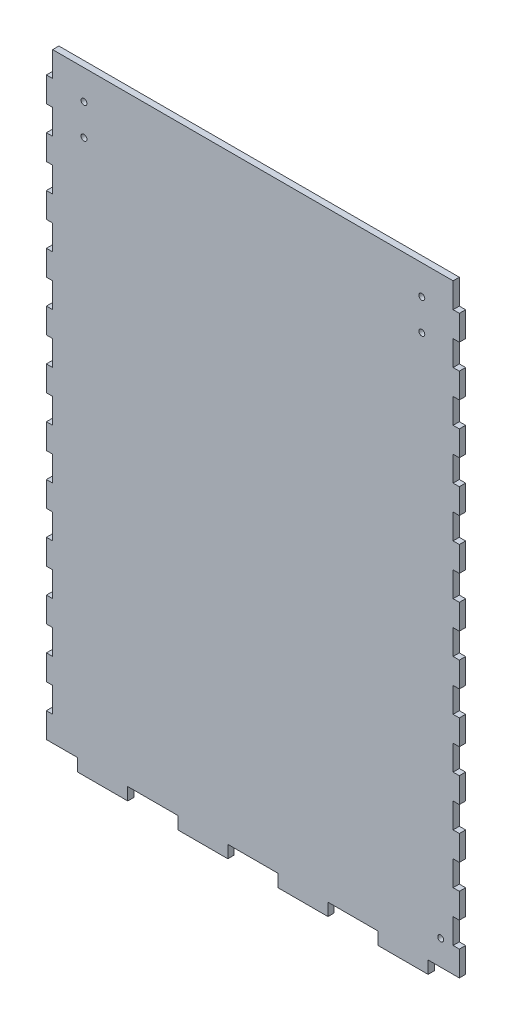
SolidWorks part; units mm, degrees
material "Acrylic (Medium-high impact)"
ref_plane "Front Plane" through (0, 0, 0) normal (0, 0, 1) x (1, 0, 0)
ref_plane "Top Plane" through (0, 0, 0) normal (0, 1, 0) x (1, 0, 0)
ref_plane "Right Plane" through (0, 0, 0) normal (1, 0, 0) x (0, 0, -1)
sketch "Sketch1" plane through (0, 0, 0) normal (0, 0, 1) x (1, 0, 0)
  line L0 (0, 0) -> (203.2, 0)
  line L1 (203.2, 0) -> (203.2, 304.8)
  line L2 (203.2, 304.8) -> (0, 304.8)
  line L3 (0, 304.8) -> (0, 0)
  dimension "D1" = 203.2
  dimension "D2" = 304.8
extrude "Boss-Extrude1" add sketch "Sketch1" along normal blind 3.175
sketch "Sketch2" plane through (0, 0, 3.175) normal (0, 0, 1) x (1, 0, 0)
  line L0 (0, 304.8) -> (-3.175, 304.8)
  line L1 (-3.175, 304.8) -> (-3.175, 292.1)
  line L2 (-3.175, 292.1) -> (0, 292.1)
  line L3 (0, 304.8) -> (0, 0) construction
  line L4 (0, 292.1) -> (0, 304.8)
  line L5 (101.6, 304.8) -> (101.6, 0) construction
  line L6 (203.2, 304.8) -> (0, 304.8) construction
  line L7 (0, 0) -> (203.2, 0) construction
  line L8 (206.375, 292.1) -> (203.2, 292.1)
  line L9 (206.375, 304.8) -> (206.375, 292.1)
  line L10 (203.2, 304.8) -> (206.375, 304.8)
  line L11 (203.2, 292.1) -> (203.2, 304.8)
  line L12 (0, 266.7) -> (0, 279.4)
  line L13 (0, 279.4) -> (-3.175, 279.4)
  line L14 (-3.175, 279.4) -> (-3.175, 266.7)
  line L15 (-3.175, 266.7) -> (0, 266.7)
  line L16 (206.375, 266.7) -> (203.2, 266.7)
  line L17 (203.2, 266.7) -> (203.2, 279.4)
  line L18 (203.2, 279.4) -> (206.375, 279.4)
  line L19 (206.375, 279.4) -> (206.375, 266.7)
  line L20 (0, 241.3) -> (0, 254)
  line L21 (0, 254) -> (-3.175, 254)
  line L22 (-3.175, 254) -> (-3.175, 241.3)
  line L23 (-3.175, 241.3) -> (0, 241.3)
  line L24 (206.375, 241.3) -> (203.2, 241.3)
  line L25 (203.2, 241.3) -> (203.2, 254)
  line L26 (203.2, 254) -> (206.375, 254)
  line L27 (206.375, 254) -> (206.375, 241.3)
  line L28 (0, 215.9) -> (0, 228.6)
  line L29 (0, 228.6) -> (-3.175, 228.6)
  line L30 (-3.175, 228.6) -> (-3.175, 215.9)
  line L31 (-3.175, 215.9) -> (0, 215.9)
  line L32 (206.375, 215.9) -> (203.2, 215.9)
  line L33 (203.2, 215.9) -> (203.2, 228.6)
  line L34 (203.2, 228.6) -> (206.375, 228.6)
  line L35 (206.375, 228.6) -> (206.375, 215.9)
  line L36 (0, 190.5) -> (0, 203.2)
  line L37 (0, 203.2) -> (-3.175, 203.2)
  line L38 (-3.175, 203.2) -> (-3.175, 190.5)
  line L39 (-3.175, 190.5) -> (0, 190.5)
  line L40 (206.375, 190.5) -> (203.2, 190.5)
  line L41 (203.2, 190.5) -> (203.2, 203.2)
  line L42 (203.2, 203.2) -> (206.375, 203.2)
  line L43 (206.375, 203.2) -> (206.375, 190.5)
  line L44 (0, 165.1) -> (0, 177.8)
  line L45 (0, 177.8) -> (-3.175, 177.8)
  line L46 (-3.175, 177.8) -> (-3.175, 165.1)
  line L47 (-3.175, 165.1) -> (0, 165.1)
  line L48 (206.375, 165.1) -> (203.2, 165.1)
  line L49 (203.2, 165.1) -> (203.2, 177.8)
  line L50 (203.2, 177.8) -> (206.375, 177.8)
  line L51 (206.375, 177.8) -> (206.375, 165.1)
  line L52 (0, 139.7) -> (0, 152.4)
  line L53 (0, 152.4) -> (-3.175, 152.4)
  line L54 (-3.175, 152.4) -> (-3.175, 139.7)
  line L55 (-3.175, 139.7) -> (0, 139.7)
  line L56 (206.375, 139.7) -> (203.2, 139.7)
  line L57 (203.2, 139.7) -> (203.2, 152.4)
  line L58 (203.2, 152.4) -> (206.375, 152.4)
  line L59 (206.375, 152.4) -> (206.375, 139.7)
  line L60 (0, 114.3) -> (0, 127)
  line L61 (0, 127) -> (-3.175, 127)
  line L62 (-3.175, 127) -> (-3.175, 114.3)
  line L63 (-3.175, 114.3) -> (0, 114.3)
  line L64 (206.375, 114.3) -> (203.2, 114.3)
  line L65 (203.2, 114.3) -> (203.2, 127)
  line L66 (203.2, 127) -> (206.375, 127)
  line L67 (206.375, 127) -> (206.375, 114.3)
  line L68 (0, 88.9) -> (0, 101.6)
  line L69 (0, 101.6) -> (-3.175, 101.6)
  line L70 (-3.175, 101.6) -> (-3.175, 88.9)
  line L71 (-3.175, 88.9) -> (0, 88.9)
  line L72 (206.375, 88.9) -> (203.2, 88.9)
  line L73 (203.2, 88.9) -> (203.2, 101.6)
  line L74 (203.2, 101.6) -> (206.375, 101.6)
  line L75 (206.375, 101.6) -> (206.375, 88.9)
  line L76 (0, 63.5) -> (0, 76.2)
  line L77 (0, 76.2) -> (-3.175, 76.2)
  line L78 (-3.175, 76.2) -> (-3.175, 63.5)
  line L79 (-3.175, 63.5) -> (0, 63.5)
  line L80 (206.375, 63.5) -> (203.2, 63.5)
  line L81 (203.2, 63.5) -> (203.2, 76.2)
  line L82 (203.2, 76.2) -> (206.375, 76.2)
  line L83 (206.375, 76.2) -> (206.375, 63.5)
  line L84 (0, 38.1) -> (0, 50.8)
  line L85 (0, 50.8) -> (-3.175, 50.8)
  line L86 (-3.175, 50.8) -> (-3.175, 38.1)
  line L87 (-3.175, 38.1) -> (0, 38.1)
  line L88 (206.375, 38.1) -> (203.2, 38.1)
  line L89 (203.2, 38.1) -> (203.2, 50.8)
  line L90 (203.2, 50.8) -> (206.375, 50.8)
  line L91 (206.375, 50.8) -> (206.375, 38.1)
  line L92 (0, 12.7) -> (0, 25.4)
  line L93 (0, 25.4) -> (-3.175, 25.4)
  line L94 (-3.175, 25.4) -> (-3.175, 12.7)
  line L95 (-3.175, 12.7) -> (0, 12.7)
  line L96 (206.375, 12.7) -> (203.2, 12.7)
  line L97 (203.2, 12.7) -> (203.2, 25.4)
  line L98 (203.2, 25.4) -> (206.375, 25.4)
  line L99 (206.375, 25.4) -> (206.375, 12.7)
  line L100 (0, 292.1) -> (0, 266.7) construction
  line L101 (12.7, 0) -> (12.7, -6.35)
  line L102 (12.7, -6.35) -> (38.1, -6.35)
  line L103 (38.1, -6.35) -> (38.1, 0)
  line L104 (38.1, 0) -> (12.7, 0)
  line L105 (88.9, 0) -> (63.5, 0)
  line L106 (63.5, 0) -> (63.5, -6.35)
  line L107 (63.5, -6.35) -> (88.9, -6.35)
  line L108 (88.9, -6.35) -> (88.9, 0)
  line L109 (139.7, 0) -> (114.3, 0)
  line L110 (114.3, 0) -> (114.3, -6.35)
  line L111 (114.3, -6.35) -> (139.7, -6.35)
  line L112 (139.7, -6.35) -> (139.7, 0)
  line L113 (190.5, 0) -> (165.1, 0)
  line L114 (165.1, 0) -> (165.1, -6.35)
  line L115 (165.1, -6.35) -> (190.5, -6.35)
  line L116 (190.5, -6.35) -> (190.5, 0)
  line L117 (38.1, 0) -> (88.9, 0) construction
  dimension "D1" = 3.175
  dimension "D2" = 12.7
  dimension "D4" = 25.4
  dimension "D5" = 12.7
  dimension "D6" = 6.35
  dimension "D7" = 25.4
  dimension "D9" = 50.8
  dimension "D3" = 12
  dimension "D8" = 4
extrude "Boss-Extrude2" [suppressed] add sketch "Sketch2" against normal up to surface (3.175 mm away) up to face at (101.6, 152.4, 0)
sketch "Sketch3" plane through (0, 0, 3.175) normal (0, 0, 1) x (1, 0, 0)
  line L0 (0, 0) -> (-3.175, 0)
  line L1 (-3.175, 0) -> (-3.175, 12.7)
  line L2 (-3.175, 12.7) -> (0, 12.7)
  line L3 (0, 304.8) -> (0, 0) construction
  line L4 (0, 12.7) -> (0, 0)
  line L5 (101.6, 304.8) -> (101.6, 0) construction
  line L6 (203.2, 304.8) -> (0, 304.8) construction
  line L7 (0, 0) -> (203.2, 0) construction
  line L8 (206.375, 12.7) -> (203.2, 12.7)
  line L9 (206.375, 0) -> (206.375, 12.7)
  line L10 (203.2, 0) -> (206.375, 0)
  line L11 (203.2, 12.7) -> (203.2, 0)
  line L12 (0, 38.1) -> (0, 25.4)
  line L13 (0, 25.4) -> (-3.175, 25.4)
  line L14 (-3.175, 25.4) -> (-3.175, 38.1)
  line L15 (-3.175, 38.1) -> (0, 38.1)
  line L16 (206.375, 38.1) -> (203.2, 38.1)
  line L17 (203.2, 38.1) -> (203.2, 25.4)
  line L18 (203.2, 25.4) -> (206.375, 25.4)
  line L19 (206.375, 25.4) -> (206.375, 38.1)
  line L20 (0, 63.5) -> (0, 50.8)
  line L21 (0, 50.8) -> (-3.175, 50.8)
  line L22 (-3.175, 50.8) -> (-3.175, 63.5)
  line L23 (-3.175, 63.5) -> (0, 63.5)
  line L24 (206.375, 63.5) -> (203.2, 63.5)
  line L25 (203.2, 63.5) -> (203.2, 50.8)
  line L26 (203.2, 50.8) -> (206.375, 50.8)
  line L27 (206.375, 50.8) -> (206.375, 63.5)
  line L28 (0, 88.9) -> (0, 76.2)
  line L29 (0, 76.2) -> (-3.175, 76.2)
  line L30 (-3.175, 76.2) -> (-3.175, 88.9)
  line L31 (-3.175, 88.9) -> (0, 88.9)
  line L32 (206.375, 88.9) -> (203.2, 88.9)
  line L33 (203.2, 88.9) -> (203.2, 76.2)
  line L34 (203.2, 76.2) -> (206.375, 76.2)
  line L35 (206.375, 76.2) -> (206.375, 88.9)
  line L36 (0, 114.3) -> (0, 101.6)
  line L37 (0, 101.6) -> (-3.175, 101.6)
  line L38 (-3.175, 101.6) -> (-3.175, 114.3)
  line L39 (-3.175, 114.3) -> (0, 114.3)
  line L40 (206.375, 114.3) -> (203.2, 114.3)
  line L41 (203.2, 114.3) -> (203.2, 101.6)
  line L42 (203.2, 101.6) -> (206.375, 101.6)
  line L43 (206.375, 101.6) -> (206.375, 114.3)
  line L44 (0, 139.7) -> (0, 127)
  line L45 (0, 127) -> (-3.175, 127)
  line L46 (-3.175, 127) -> (-3.175, 139.7)
  line L47 (-3.175, 139.7) -> (0, 139.7)
  line L48 (206.375, 139.7) -> (203.2, 139.7)
  line L49 (203.2, 139.7) -> (203.2, 127)
  line L50 (203.2, 127) -> (206.375, 127)
  line L51 (206.375, 127) -> (206.375, 139.7)
  line L52 (0, 165.1) -> (0, 152.4)
  line L53 (0, 152.4) -> (-3.175, 152.4)
  line L54 (-3.175, 152.4) -> (-3.175, 165.1)
  line L55 (-3.175, 165.1) -> (0, 165.1)
  line L56 (206.375, 165.1) -> (203.2, 165.1)
  line L57 (203.2, 165.1) -> (203.2, 152.4)
  line L58 (203.2, 152.4) -> (206.375, 152.4)
  line L59 (206.375, 152.4) -> (206.375, 165.1)
  line L60 (0, 190.5) -> (0, 177.8)
  line L61 (0, 177.8) -> (-3.175, 177.8)
  line L62 (-3.175, 177.8) -> (-3.175, 190.5)
  line L63 (-3.175, 190.5) -> (0, 190.5)
  line L64 (206.375, 190.5) -> (203.2, 190.5)
  line L65 (203.2, 190.5) -> (203.2, 177.8)
  line L66 (203.2, 177.8) -> (206.375, 177.8)
  line L67 (206.375, 177.8) -> (206.375, 190.5)
  line L68 (0, 215.9) -> (0, 203.2)
  line L69 (0, 203.2) -> (-3.175, 203.2)
  line L70 (-3.175, 203.2) -> (-3.175, 215.9)
  line L71 (-3.175, 215.9) -> (0, 215.9)
  line L72 (206.375, 215.9) -> (203.2, 215.9)
  line L73 (203.2, 215.9) -> (203.2, 203.2)
  line L74 (203.2, 203.2) -> (206.375, 203.2)
  line L75 (206.375, 203.2) -> (206.375, 215.9)
  line L76 (0, 241.3) -> (0, 228.6)
  line L77 (0, 228.6) -> (-3.175, 228.6)
  line L78 (-3.175, 228.6) -> (-3.175, 241.3)
  line L79 (-3.175, 241.3) -> (0, 241.3)
  line L80 (206.375, 241.3) -> (203.2, 241.3)
  line L81 (203.2, 241.3) -> (203.2, 228.6)
  line L82 (203.2, 228.6) -> (206.375, 228.6)
  line L83 (206.375, 228.6) -> (206.375, 241.3)
  line L84 (0, 266.7) -> (0, 254)
  line L85 (0, 254) -> (-3.175, 254)
  line L86 (-3.175, 254) -> (-3.175, 266.7)
  line L87 (-3.175, 266.7) -> (0, 266.7)
  line L88 (206.375, 266.7) -> (203.2, 266.7)
  line L89 (203.2, 266.7) -> (203.2, 254)
  line L90 (203.2, 254) -> (206.375, 254)
  line L91 (206.375, 254) -> (206.375, 266.7)
  line L92 (0, 292.1) -> (0, 279.4)
  line L93 (0, 279.4) -> (-3.175, 279.4)
  line L94 (-3.175, 279.4) -> (-3.175, 292.1)
  line L95 (-3.175, 292.1) -> (0, 292.1)
  line L96 (206.375, 292.1) -> (203.2, 292.1)
  line L97 (203.2, 292.1) -> (203.2, 279.4)
  line L98 (203.2, 279.4) -> (206.375, 279.4)
  line L99 (206.375, 279.4) -> (206.375, 292.1)
  line L100 (0, 12.7) -> (0, 38.1) construction
  line L101 (12.7, 0) -> (12.7, -6.35)
  line L102 (12.7, -6.35) -> (38.1, -6.35)
  line L103 (38.1, -6.35) -> (38.1, 0)
  line L104 (38.1, 0) -> (12.7, 0)
  line L105 (88.9, 0) -> (63.5, 0)
  line L106 (63.5, 0) -> (63.5, -6.35)
  line L107 (63.5, -6.35) -> (88.9, -6.35)
  line L108 (88.9, -6.35) -> (88.9, 0)
  line L109 (139.7, 0) -> (114.3, 0)
  line L110 (114.3, 0) -> (114.3, -6.35)
  line L111 (114.3, -6.35) -> (139.7, -6.35)
  line L112 (139.7, -6.35) -> (139.7, 0)
  line L113 (190.5, 0) -> (165.1, 0)
  line L114 (165.1, 0) -> (165.1, -6.35)
  line L115 (165.1, -6.35) -> (190.5, -6.35)
  line L116 (190.5, -6.35) -> (190.5, 0)
  line L117 (38.1, 0) -> (88.9, 0) construction
  dimension "D1" = 3.175
  dimension "D2" = 12.7
  dimension "D9" = 50.8
  dimension "D3" = 12
  dimension "D8" = 4
  dimension "D4" = 25.4
  dimension "D5" = 6.35
  dimension "D6" = 25.4
  dimension "D7" = 12.7
sketch "Sketch4" [suppressed] plane through (0, 0, 3.175) normal (0, 0, 1) x (1, 0, 0)
  line L0 (50.8, 33.5) -> (50.8, 66.5) construction
  line L1 (34.3, 50) -> (67.3, 50) construction
  line L2 (0, 12.7) -> (0, 0) construction
  line L3 (88.9, 0) -> (114.3, 0) construction
  circle A0 centre (50.8, 50) radius 16.5
  circle A1 centre (25.8, 75) radius 1.5
  circle A5 centre (75.8, 75) radius 1.5
  circle A6 centre (75.8, 25) radius 1.5
  circle A7 centre (25.8, 25) radius 1.5
  dimension "D5" = 33
  dimension "D6" = 3
  dimension "D1" = 50
  dimension "D2" = 50
  dimension "D3" = 60
  dimension "D4" = 50
extrude "Cut-Extrude1" [suppressed] cut sketch "Sketch4" against normal up to surface (3.175 mm away) up to face at (101.6, 152.4, 0)
sketch "Sketch5" [suppressed] plane through (0, 0, 0) normal (0, 0, -1) x (-1, 0, 0)
  line L1 (-206.375, 304.8) -> (-206.375, 292.1) construction
  line L2 (-206.375, 304.8) -> (3.175, 304.8) construction
  line L3 (-101.6, 304.8) -> (-101.6, 0) construction
  line L4 (-88.9, 0) -> (-114.3, 0) construction
  circle A1 centre (-187.325, 289.8) radius 1.5
  circle A2 centre (-187.325, 274.05) radius 1.5
  circle A3 centre (-15.875, 274.05) radius 1.5
  circle A4 centre (-15.875, 289.8) radius 1.5
  dimension "D1" = 3
  dimension "D2" = 3
  dimension "D3" = 15.75
  dimension "D4" = 19.05
  dimension "D5" = 15
extrude "Cut-Extrude2" [suppressed] cut sketch "Sketch5" against normal up to surface (3.175 mm away) up to face at (101.6, 152.4, 3.175)
extrude "Boss-Extrude4" add sketch "Sketch3" against normal up to surface (3.175 mm away) up to face at (101.6, 152.4, 0)
sketch "Sketch6" plane through (0, 0, 0) normal (0, 0, -1) x (-1, 0, 0)
  line L1 (-203.2, 304.8) -> (0, 304.8) construction
  line L2 (-101.6, 304.8) -> (-101.6, 0) construction
  line L3 (-88.9, 0) -> (-114.3, 0) construction
  line L4 (-206.375, 292.1) -> (-206.375, 279.4) construction
  circle A0 centre (-187.325, 289.8) radius 1.5
  circle A1 centre (-187.325, 274.05) radius 1.5
  circle A2 centre (-15.875, 274.05) radius 1.5
  circle A3 centre (-15.875, 289.8) radius 1.5
  dimension "D1" = 3
  dimension "D2" = 3
  dimension "D3" = 19.05
  dimension "D4" = 15
  dimension "D5" = 15.75
extrude "Cut-Extrude3" cut sketch "Sketch6" against normal up to surface (3.175 mm away) up to face at (101.6, 130.175, 3.175)
sketch "Sketch7" [suppressed] plane through (0, 0, 3.175) normal (0, 0, 1) x (1, 0, 0)
  line L0 (159.0125, 24.45) -> (159.0125, 12.011)
  line L1 (159.0125, 12.011) -> (189.5875, 12.011)
  line L2 (189.5875, 12.011) -> (189.5875, 24.45)
  line L3 (189.5875, 24.45) -> (159.0125, 24.45)
  line L4 (206.375, 12.7) -> (206.375, 25.4) construction
  line L5 (190.5, 0) -> (203.2, 0) construction
  dimension "D1" = 16.7875
  dimension "D2" = 24.45
  dimension "D3" = 12.439
  dimension "D4" = 30.575
extrude "Cut-Extrude4" [suppressed] cut sketch "Sketch7" against normal up to surface (3.175 mm away) up to face at (17.375, 289.8, 0)
sketch "Sketch8" plane through (0, 0, 3.175) normal (0, 0, 1) x (1, 0, 0)
  line L0 (203.2, 12.7) -> (203.2, 25.4) construction
  line L1 (190.5, 0) -> (206.375, 0) construction
  circle A0 centre (196.9135, 12.7) radius 1.5
  dimension "D1" = 3
  dimension "D2" = 6.2865
  dimension "D3" = 12.7
extrude "Cut-Extrude5" cut sketch "Sketch8" against normal up to surface (3.175 mm away) up to face at (17.375, 289.8, 0)
equation "\"wall_thickness\"= 0.125in"
equation "\"base_thickness\"= 0.25in"
equation "\"D1@Boss-Extrude1\"=\"wall_thickness\""
equation "\"D1@Sketch2\"=\"wall_thickness\""
equation "\"D6@Sketch2\"=\"base_thickness\""
equation "\"D1@Sketch3\"=\"wall_thickness\""
equation "\"D5@Sketch3\"=\"base_thickness\""
